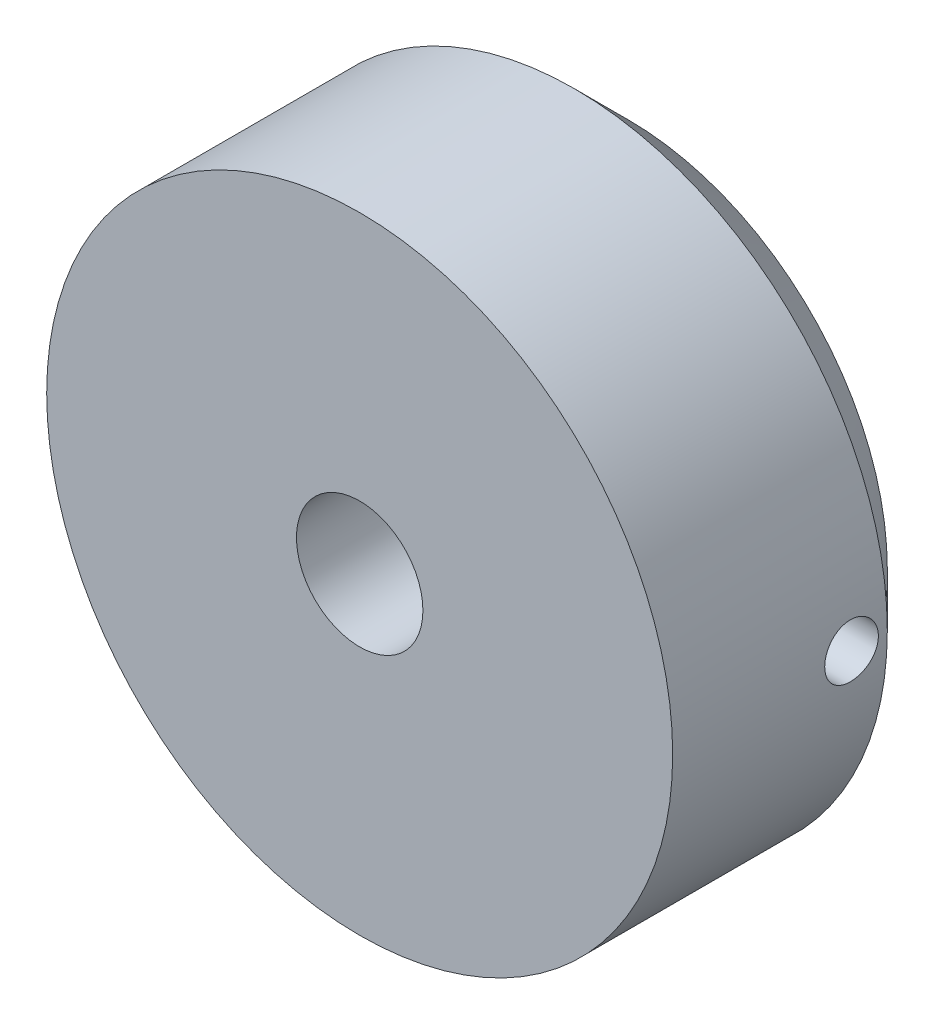
SolidWorks part; units mm, degrees
ref_plane "Front Plane" through (0, 0, 0) normal (0, 0, 1) x (1, 0, 0)
ref_plane "Top Plane" through (0, 0, 0) normal (0, 1, 0) x (1, 0, 0)
ref_plane "Right Plane" through (0, 0, 0) normal (1, 0, 0) x (0, 0, -1)
ref_axis "Z" through (0, 0, 543.0939) along (0, 0, -1)
ref_axis "X" through (17.0818, 0, 0) along (-1, 0, 0)
ref_axis "Y" through (0, 20.242, 0) along (0, -1, 0)
sketch "Sketch1" plane through (0, 0, 0) normal (0, 0, 1) x (1, 0, 0)
  circle A0 centre (0, 0) radius 17.5
  circle A1 centre (0, 0) radius 3.535
  dimension "D1" = 35
  dimension "D2" = 7.07
extrude "Boss-Extrude1" add sketch "Sketch1" against normal blind 5 and the other way blind 10
sketch "Sketch2" plane through (0, 0, 0) normal (0, 1, 0) x (1, 0, 0)
  line L0 (-16.3173, 0) -> (16.3173, 0) construction
  line L1 (0, -20.5521) -> (0, 20.5521) construction
  circle A0 centre (0, 0) radius 1.5
  dimension "D1" = 3
extrude "Cut-Extrude1" cut sketch "Sketch2" against normal through all
sketch "Sketch3" plane through (0, 0, 0) normal (1, 0, 0) x (0, 0, -1)
  circle A0 centre (0, 0) radius 1.5
  dimension "D1" = 3
extrude "Cut-Extrude2" cut sketch "Sketch3" along normal through all
chamfer "Chamfer1" distance 3 angle 45 1 edges at (17.5, 0, -5)
sketch "Sketch4" plane through (0, 0, 0) normal (0, 0, 1) x (1, 0, 0)
  circle A0 centre (0, 0) radius 3.535
  circle A2 centre (0, 0) radius 3.535 construction
  circle A3 centre (0, 0) radius 11.5
  dimension "D1" = 23
extrude "Boss-Extrude2" add sketch "Sketch4" along normal up to surface and the other way up to surface up to face at (17.5, 0, 10) other way up to face at (14.5, 0, -5)
sketch "Sketch5" plane through (0, 0, 0) normal (0, 0, 1) x (1, 0, 0)
  line L0 (0, 0) -> (0, -37.34) construction
  dimension "D1" = 37.34
equation "\"EyeDiameter\" = 35"
equation "\"BasePlaneDistance\" = \"EyeDiameter\"/2+19.84"
equation "\"EyeClearance\" = 2"
equation "\"EyeOD\"= \"EyeDiameter\""
equation "\"D1@Sketch1\"=\"EyeOD\""
equation "\"D2@Sketch1\"= 7.07"
equation "\"pinHoleDiameter\"= 3"
equation "\"D1@Sketch2\"=\"pinHoleDiameter\""
equation "\"D1@Sketch3\"=\"pinHoleDiameter\""
equation "\"D1@Sketch4\"=\"EyeDiameter\"-12"
equation "\"D1@Sketch5\"=\"BasePlaneDistance\""
